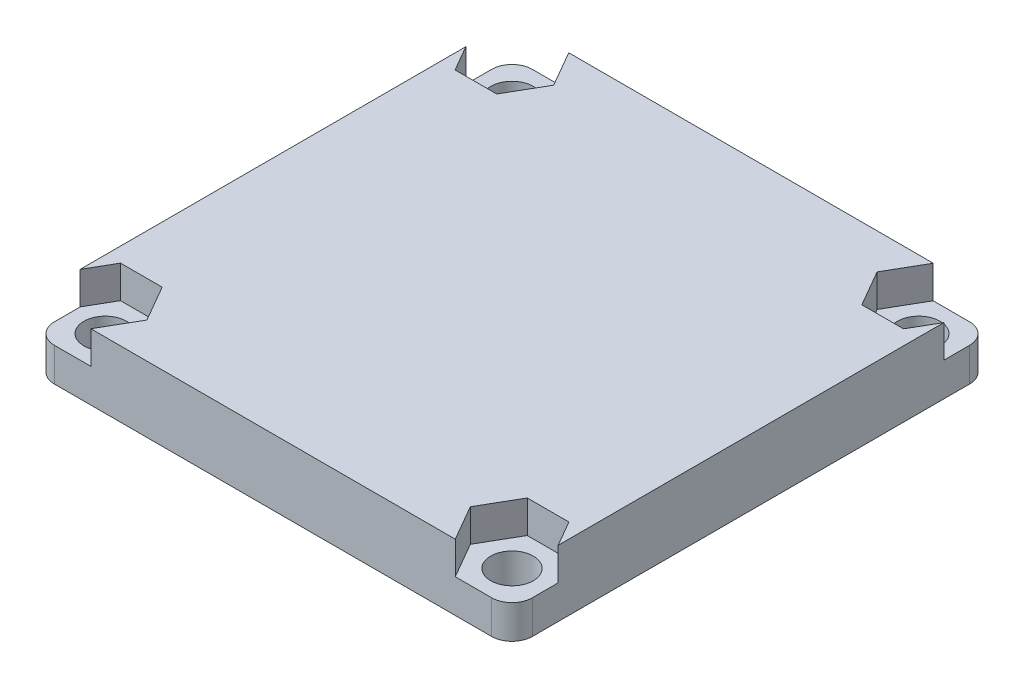
SolidWorks part; units mm, degrees
ref_plane "Спереди" through (0, 0, 0) normal (0, 0, 1) x (1, 0, 0)
ref_plane "Сверху" through (0, 0, 0) normal (0, 1, 0) x (1, 0, 0)
ref_plane "Справа" through (0, 0, 0) normal (1, 0, 0) x (0, 0, -1)
sketch "Эскиз1" plane through (0, 0, 0) normal (0, 1, 0) x (1, 0, 0)
  line L1 (0, 0) -> (-47, 0)
  line L2 (0, 0) -> (0, 47)
  line L3 (0, 47) -> (-47, 47)
  line L4 (-47, 0) -> (-47, 47)
  dimension "D1" = 47
  dimension "D2" = 47
extrude "Бобышка-Вытянуть1" add sketch "Эскиз1" along normal blind 6.5
sketch "Эскиз2" plane through (0, 0, 0) normal (0, -1, 0) x (1, 0, 0)
  line L0 (-47, 0) -> (0, 0) construction
  line L1 (-47, -47) -> (-47, 0) construction
  line L2 (-47, -23.5) -> (0, -23.5) construction
  line L3 (0, 0) -> (0, -47) construction
  line L4 (-23.5, -47) -> (-23.5, 0) construction
  line L5 (0, -47) -> (-47, -47) construction
  circle A0 centre (-43.5, -3.5) radius 2.1
  circle A1 centre (-3.5, -3.5) radius 2.1
  circle A2 centre (-3.5, -43.5) radius 2.1
  circle A3 centre (-43.5, -43.5) radius 2.1
  dimension "D1" = 4.2
  dimension "D2" = 3.5
  dimension "D3" = 3.5
extrude "Вырез-Вытянуть1" cut sketch "Эскиз2" against normal through all
sketch "Эскиз3" plane through (0, 0, 0) normal (0, -1, 0) x (1, 0, 0)
  line L0 (-47, -47) -> (-47, 0) construction
  line L1 (-40.8, -6.2) -> (-6.2, -6.2)
  line L2 (-40.8, -6.2) -> (-40.8, -40.8)
  line L3 (-40.8, -40.8) -> (-6.2, -40.8)
  line L4 (-6.2, -6.2) -> (-6.2, -40.8)
  line L5 (0, 0) -> (0, -47) construction
  line L6 (-47, 0) -> (0, 0) construction
  line L7 (0, -47) -> (-47, -47) construction
  dimension "D1" = 6.2
  dimension "D2" = 6.2
  dimension "D3" = 6.2
  dimension "D4" = 6.2
extrude "Вырез-Вытянуть2" cut sketch "Эскиз3" against normal blind 2
fillet "Скругление1" radius 2 4 edges at (0, 3.25, -47) (-47, 3.25, -47) (-47, 3.25, 0) (0, 3.25, 0)
fillet "Скругление2" radius 1.5 4 edges at (-6.2, 2, -23.5) (-23.5, 2, -6.2) (-23.5, 2, -40.8) (-40.8, 2, -23.5)
fillet "Скругление3" radius 1.5 8 edges at (-6.6393, 1.5607, -40.3607) (-40.3607, 1.5607, -40.3607) (-6.6393, 1.5607, -6.6393) (-40.3607, 1.5607, -6.6393) (-6.2, 0.25, -40.8) (-40.8, 0.25, -40.8) (-6.2, 0.25, -6.2) (-40.8, 0.25, -6.2)
sketch "Эскиз4" plane through (0, 6.5, 0) normal (0, 1, 0) x (1, 0, 0)
  line L0 (-2, 47) -> (-45, 47) construction
  line L5 (-47, 45) -> (-47, 2) construction
  line L6 (-23.5, 47) -> (-23.5, 0) construction
  line L7 (-45, 0) -> (-2, 0) construction
  line L8 (0, 23.5) -> (-47, 23.5) construction
  line L9 (0, 2) -> (0, 45) construction
  line L22 (-5.5496, 39.95) -> (-7.5992, 43.5)
  line L23 (-39.4008, 43.5) -> (-41.4504, 47.05)
  line L24 (-41.4504, 47.05) -> (-45.5496, 47.05)
  line L25 (-45.5496, 47.05) -> (-47.5992, 43.5)
  line L26 (-47.5992, 43.5) -> (-45.5496, 39.95)
  line L27 (-45.5496, 39.95) -> (-41.4504, 39.95)
  line L28 (-41.4504, 39.95) -> (-39.4008, 43.5)
  line L29 (-1.4504, 39.95) -> (-5.5496, 39.95)
  line L30 (0.5992, 43.5) -> (-1.4504, 39.95)
  line L31 (-1.4504, 47.05) -> (0.5992, 43.5)
  line L32 (-5.5496, 47.05) -> (-1.4504, 47.05)
  line L33 (-7.5992, 43.5) -> (-5.5496, 47.05)
  line L34 (-1.4504, 7.05) -> (-5.5496, 7.05)
  line L35 (0.5992, 3.5) -> (-1.4504, 7.05)
  line L36 (-1.4504, -0.05) -> (0.5992, 3.5)
  line L37 (-5.5496, -0.05) -> (-1.4504, -0.05)
  line L38 (-7.5992, 3.5) -> (-5.5496, -0.05)
  line L39 (-5.5496, 7.05) -> (-7.5992, 3.5)
  line L40 (-41.4504, 7.05) -> (-39.4008, 3.5)
  line L41 (-45.5496, 7.05) -> (-41.4504, 7.05)
  line L42 (-47.5992, 3.5) -> (-45.5496, 7.05)
  line L43 (-45.5496, -0.05) -> (-47.5992, 3.5)
  line L44 (-41.4504, -0.05) -> (-45.5496, -0.05)
  line L45 (-39.4008, 3.5) -> (-41.4504, -0.05)
  circle A0 centre (-43.5, 43.5) radius 2.1 construction
  circle A1 centre (-43.5, 43.5) radius 3.55 construction
  dimension "D1" = 7.1
extrude "Вырез-Вытянуть3" cut sketch "Эскиз4" against normal blind 3.2
sketch "Эскиз5" plane through (0, 6.5, 0) normal (0, 1, 0) x (1, 0, 0)
  line L0 (-41.4215, 47) -> (-45, 47) construction
  line L1 (-43.2108, 47) -> (-47, 47)
  line L2 (-43.2108, 47) -> (-43.2108, 43.5)
  line L3 (-43.2108, 43.5) -> (-47, 43.5)
  line L4 (-47, 47) -> (-47, 43.5)
  line L5 (-47, 44.5378) -> (-47, 42.4622) construction
  line L6 (-23.5, 47) -> (-23.5, 0) construction
  line L7 (-5.5785, 47) -> (-41.4215, 47) construction
  line L8 (-41.4215, 0) -> (-5.5785, 0) construction
  line L9 (0, 23.5) -> (-47, 23.5) construction
  line L10 (0, 4.5378) -> (0, 42.4622) construction
  line L11 (-47, 42.4622) -> (-47, 4.5378) construction
  line L12 (-3.7892, 43.5) -> (0, 43.5)
  line L13 (0, 47) -> (0, 43.5)
  line L14 (-3.7892, 47) -> (0, 47)
  line L15 (-3.7892, 47) -> (-3.7892, 43.5)
  line L16 (-43.2108, 3.5) -> (-47, 3.5)
  line L17 (-47, 0) -> (-47, 3.5)
  line L18 (-43.2108, 0) -> (-47, 0)
  line L19 (-43.2108, 0) -> (-43.2108, 3.5)
  line L20 (-3.7892, 0) -> (-3.7892, 3.5)
  line L21 (-3.7892, 0) -> (0, 0)
  line L22 (0, 0) -> (0, 3.5)
  line L23 (-3.7892, 3.5) -> (0, 3.5)
extrude "Вырез-Вытянуть4" cut sketch "Эскиз5" against normal blind 3.2
